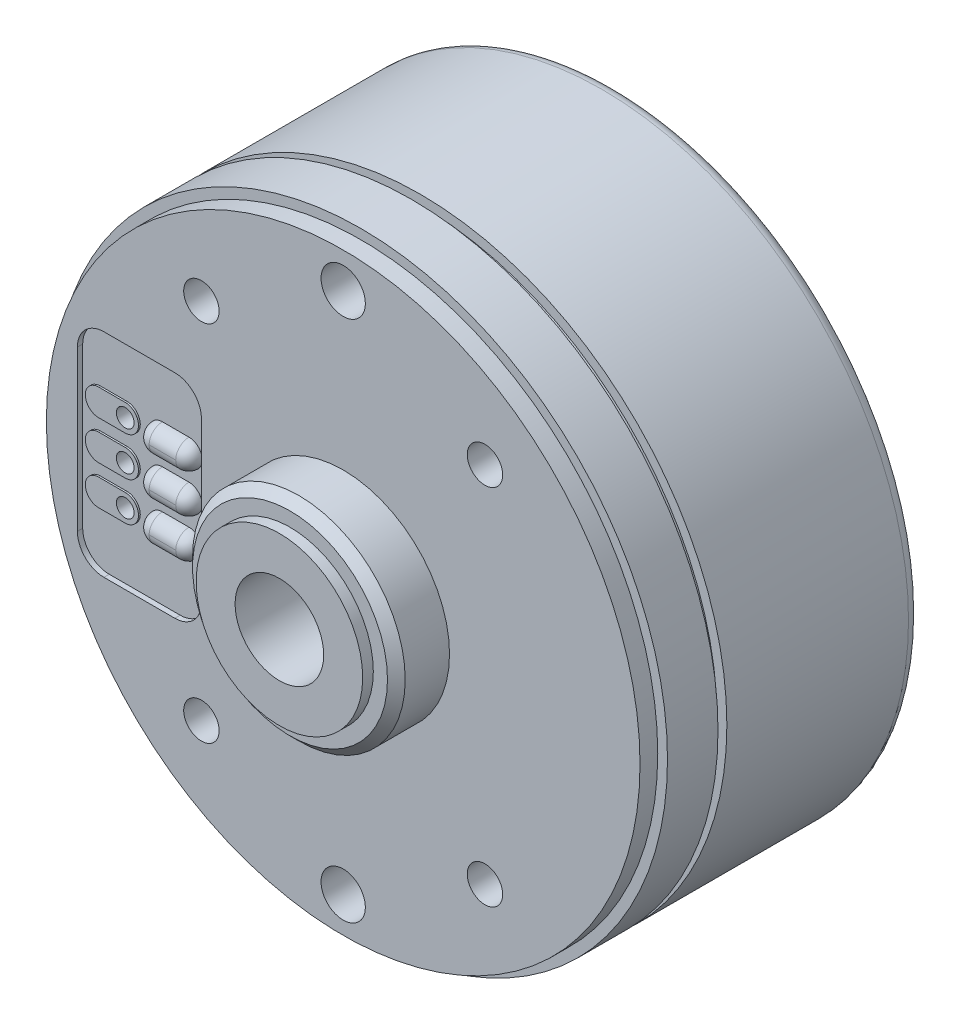
SolidWorks part; units mm, degrees
ref_plane "前视基准面" through (0, 0, 0) normal (0, 0, 1) x (1, 0, 0)
ref_plane "上视基准面" through (0, 0, 0) normal (0, 1, 0) x (1, 0, 0)
ref_plane "右视基准面" through (0, 0, 0) normal (1, 0, 0) x (0, 0, -1)
sketch "草图1" plane through (0, 0, 0) normal (0, 0, 1) x (1, 0, 0)
  line L0 (-101.7763, 0) -> (126.1391, 0) construction
  line L1 (0, -98.9517) -> (0, 107.9553) construction
  line L2 (0, 0) -> (13.767, 17.639) construction
  line L3 (8, 10.25) -> (-8, 10.25) construction
  line L4 (0, 0) -> (-13.767, 17.639) construction
  line L8 (8, 10.25) -> (8, -10.25) construction
  line L9 (8, -10.25) -> (-8, -10.25) construction
  line L10 (-8, 10.25) -> (-8, -10.25) construction
  line L11 (-11.5, -6.8575) -> (-11.5, 7.1069) construction
  line L12 (-9.5, 6) -> (-13.5, 6)
  line L13 (-8, 4.5) -> (-8, -4.5)
  line L14 (-9.5, -6) -> (-13.5, -6)
  line L15 (-15, 4.5) -> (-15, -4.5)
  line L16 (-12.5, 0) -> (-14, 0) construction
  line L17 (-12.5, -0.75) -> (-14, -0.75)
  line L18 (-12.5, 0.75) -> (-14, 0.75)
  line L19 (-12.5, 2.2) -> (-14, 2.2) construction
  line L20 (-12.5, 1.45) -> (-14, 1.45)
  line L21 (-12.5, 2.95) -> (-14, 2.95)
  line L22 (-12.5, -2.2) -> (-14, -2.2) construction
  line L23 (-12.5, -2.95) -> (-14, -2.95)
  line L24 (-12.5, -1.45) -> (-14, -1.45)
  line L25 (-10.5, 0) -> (-9, 0) construction
  line L26 (-10.5, -0.75) -> (-9, -0.75)
  line L27 (-10.5, 0.75) -> (-9, 0.75)
  line L28 (-10.5, -2.2) -> (-9, -2.2) construction
  line L29 (-10.5, -2.95) -> (-9, -2.95)
  line L30 (-10.5, -1.45) -> (-9, -1.45)
  line L31 (-10.5, 2.2) -> (-9, 2.2) construction
  line L32 (-10.5, 1.45) -> (-9, 1.45)
  line L33 (-10.5, 2.95) -> (-9, 2.95)
  circle A0 centre (0, 0) radius 16.75
  circle A1 centre (0, 0) radius 17.3
  circle A2 centre (0, 0) radius 14.75 construction
  circle A3 centre (0, 14.75) radius 1.25
  circle A4 centre (0, -14.75) radius 1.25
  circle A9 centre (-8, 10.25) radius 1
  circle A10 centre (8, 10.25) radius 1
  circle A11 centre (8, -10.25) radius 1
  circle A12 centre (-8, -10.25) radius 1
  circle A13 centre (0, 0) radius 6
  circle A14 centre (0, 0) radius 4.7
  circle A15 centre (0, 0) radius 2.5
  arc A16 (-8, 4.5) -> (-9.5, 6) centre (-9.5, 4.5) ccw
  arc A17 (-9.5, -6) -> (-8, -4.5) centre (-9.5, -4.5) ccw
  arc A18 (-15, -4.5) -> (-13.5, -6) centre (-13.5, -4.5) ccw
  arc A19 (-15, 4.5) -> (-13.5, 6) centre (-13.5, 4.5) cw
  arc A20 (-12.5, -0.75) -> (-12.5, 0.75) centre (-12.5, 0) ccw
  arc A21 (-14, 0.75) -> (-14, -0.75) centre (-14, 0) ccw
  arc A22 (-12.5, 1.45) -> (-12.5, 2.95) centre (-12.5, 2.2) ccw
  arc A23 (-14, 2.95) -> (-14, 1.45) centre (-14, 2.2) ccw
  arc A24 (-12.5, -2.95) -> (-12.5, -1.45) centre (-12.5, -2.2) ccw
  arc A25 (-14, -1.45) -> (-14, -2.95) centre (-14, -2.2) ccw
  arc A26 (-10.5, -0.75) -> (-10.5, 0.75) centre (-10.5, 0) cw
  arc A27 (-9, 0.75) -> (-9, -0.75) centre (-9, 0) cw
  arc A28 (-10.5, -2.95) -> (-10.5, -1.45) centre (-10.5, -2.2) cw
  arc A29 (-9, -1.45) -> (-9, -2.95) centre (-9, -2.2) cw
  arc A30 (-10.5, 1.45) -> (-10.5, 2.95) centre (-10.5, 2.2) cw
  arc A31 (-9, 2.95) -> (-9, 1.45) centre (-9, 2.2) cw
  circle A32 centre (-12.5, 0) radius 0.5
  circle A33 centre (-12.5, 2.2) radius 0.5
  circle A34 centre (-12.5, -2.2) radius 0.5
  point P36 (-8, 6)
  point P39 (-8, -6)
  point P44 (-15, 6)
  point P45 (-11.5, -6)
  point P48 (-13.25, 0)
  point P56 (-13.25, 2.2)
  point P63 (-13.25, -2.2)
  point P69 (-9.75, 0)
  point P76 (-9.75, -2.2)
  point P83 (-9.75, 2.2)
  dimension "D1" = 34.6
  dimension "D2" = 33.5
  dimension "D3" = 29.5
  dimension "D4" = 2.5
  dimension "D6" = 20.5
  dimension "D7" = 2
  dimension "D8" = 9.4
  dimension "D9" = 12
  dimension "D10" = 5
  dimension "D14" = 1.5
  dimension "D16" = 0.75
  dimension "D17" = 1.5
  dimension "D22" = 1
  dimension "D5" = 16
  dimension "D11" = 6
  dimension "D12" = 6
  dimension "D13" = 7
  dimension "D15" = 1.75
  dimension "D19" = 2.2
  dimension "D21" = 2.2
  dimension "D18" = 2
  dimension "D20" = 2
extrude "凸台-拉伸1" add sketch "草图1" along normal blind 3 contours A13
extrude "凸台-拉伸2" add sketch "草图1<3>" along normal blind 3.6 contours A14
sketch "草图1<3>" plane through (0, 0, 0) normal (0, 0, 1) x (1, 0, 0) same geometry as "草图1"
extrude "切除-拉伸1" cut sketch "草图1<4>" along normal blind 3.6 contours A15
sketch "草图1<4>" plane through (0, 0, 0) normal (0, 0, 1) x (1, 0, 0) same geometry as "草图1"
extrude "凸台-拉伸4" add sketch "草图1<7>" against normal blind 15.3 contours A1
sketch "草图1<7>" plane through (0, 0, 0) normal (0, 0, 1) x (1, 0, 0) same geometry as "草图1"
extrude "切除-拉伸3" cut sketch "草图1<8>" against normal blind 4.35 contours A1 A0 region at (-16.8107, 0, 0)
sketch "草图1<8>" plane through (0, 0, 0) normal (0, 0, 1) x (1, 0, 0) same geometry as "草图1"
extrude "凸台-拉伸3" add sketch "草图1<5>" against normal blind 3.85 contours A1
sketch "草图1<5>" plane through (0, 0, 0) normal (0, 0, 1) x (1, 0, 0) same geometry as "草图1"
extrude "切除-拉伸2" cut sketch "草图1<6>" against normal blind 1 contours A1 A0 region at (-16.8107, 0, 0)
sketch "草图1<6>" plane through (0, 0, 0) normal (0, 0, 1) x (1, 0, 0) same geometry as "草图1"
ref_plane "基准面4" through (0, 0, -15.3) normal (0, 0, -1) x (-1, 0, 0)
sketch "草图5" plane through (0, 0, -15.3) normal (0, 0, -1) x (-1, 0, 0)
  line L0 (-30.0955, 0) -> (34.2074, 0) construction
  line L1 (0, 0) -> (-19.6064, 19.6064) construction
  line L2 (0, -23.9486) -> (0, 27.9244) construction
  line L3 (5.25, 5.25) -> (5.25, -5.25) construction
  line L4 (0, 0) -> (19.6064, 19.6064) construction
  line L5 (5.25, 5.25) -> (-5.25, 5.25) construction
  line L6 (-5.25, -5.25) -> (5.25, -5.25) construction
  line L7 (-5.25, -5.25) -> (-5.25, 5.25) construction
  circle A0 centre (0, 0) radius 6.25 construction
  circle A1 centre (6.25, 0) radius 1
  circle A2 centre (0, -6.25) radius 1
  circle A3 centre (-6.25, 0) radius 1
  circle A4 centre (0, 6.25) radius 1
  circle A5 centre (5.25, 5.25) radius 1.25
  circle A6 centre (5.25, -5.25) radius 1.25
  circle A7 centre (-5.25, -5.25) radius 1.25
  circle A8 centre (-5.25, 5.25) radius 1.25
  circle A9 centre (0, 0) radius 3.25
  point P9 (0, 0)
  point P27 (0, 0)
  point P35 (0, 0)
  dimension "D1" = 12.5
  dimension "D3" = 2
  dimension "D5" = 2.5
  dimension "D7" = 6.5
  dimension "D2" = 10.5
  dimension "D4" = 4
  dimension "D6" = 4
extrude "切除-拉伸4" cut sketch "草图5" against normal blind 10.6 contours A9 region at (0, 0, -15.3)
extrude "切除-拉伸5" cut sketch "草图5<3>" against normal blind 2.5 contours A8 | A4 | A5 | A1 | A6 | A2 | A7 | A3 region at (-6.25, 0, -15.3) region at (0, -6.25, -15.3) region at (6.25, 0, -15.3) region at (0, 6.25, -15.3) region at (-5.25, 5.25, -15.3) region at (-5.25, -5.25, -15.3) region at (5.25, -5.25, -15.3) region at (5.25, 5.25, -15.3)
sketch "草图5<3>" plane through (0, 0, -15.3) normal (0, 0, -1) x (-1, 0, 0) same geometry as "草图5"
extrude "切除-拉伸6" cut sketch "草图1<9>" against normal blind 3.8 contours A3 | A10 | A11 | A4 | A12 | A9 region at (0, 14.75, 0) region at (0, -14.75, 0) region at (8, 10.25, 0) region at (8, -10.25, 0) region at (-8, -10.25, 0)
sketch "草图1<9>" plane through (0, 0, 0) normal (0, 0, 1) x (1, 0, 0) same geometry as "草图1"
fillet "圆角1" radius 0.7 1 edges at (17.3, 0, -15.3)
chamfer "倒角1" distance 0.5 angle 45 1 edges at (6, 0, 3)
extrude "切除-拉伸7" cut sketch "草图1<10>" against normal blind 10 contours A15
sketch "草图1<10>" plane through (0, 0, 0) normal (0, 0, 1) x (1, 0, 0) same geometry as "草图1"
extrude "切除-拉伸8" cut sketch "草图1<11>" against normal blind 0.3 contours L12 A19 L15 A18 L14 A17 L13 A16
sketch "草图1<11>" plane through (0, 0, 0) normal (0, 0, 1) x (1, 0, 0) same geometry as "草图1"
extrude "凸台-拉伸5" add sketch "草图1<12>" along normal blind 0.45 separate body contours A27 L27 A26 L26 | A29 L30 A28 L29 | A31 L33 A30 L32 region at (-9.75, 0, 0) region at (-9.75, -2.2, 0) region at (-9.75, 2.2, 0)
sketch "草图1<12>" plane through (0, 0, 0) normal (0, 0, 1) x (1, 0, 0) same geometry as "草图1"
extrude "凸台-拉伸6" add sketch "草图1<14>" against normal blind 0.3 contours L32 A31 L33 A30 | L26 A27 L27 A26 | L29 A29 L30 A28
sketch "草图1<14>" plane through (0, 0, 0) normal (0, 0, 1) x (1, 0, 0) same geometry as "草图1"
fillet "圆角2" radius 0.75 4 edges at (-11.25, 2.2, 0.45) (-9.75, 1.45, 0.45) (-8.25, 2.2, 0.45) (-9.75, 2.95, 0.45)
fillet "圆角3" radius 0.75 4 edges at (-11.25, 0, 0.45) (-9.75, -0.75, 0.45) (-8.25, 0, 0.45) (-9.75, 0.75, 0.45)
fillet "圆角4" radius 0.75 4 edges at (-11.25, -2.2, 0.45) (-9.75, -2.95, 0.45) (-8.25, -2.2, 0.45) (-9.75, -1.45, 0.45)
extrude "凸台-拉伸7" add sketch "草图1<15>" against normal blind 0.3 contours L17 A21 L18 A20 | L20 A23 L21 A22 | L23 A25 L24 A24
sketch "草图1<15>" plane through (0, 0, 0) normal (0, 0, 1) x (1, 0, 0) same geometry as "草图1"
extrude "切除-拉伸9" cut sketch "草图1<13>" against normal blind 2 contours A33 | A32 | A34
sketch "草图1<13>" plane through (0, 0, 0) normal (0, 0, 1) x (1, 0, 0) same geometry as "草图1"
extrude "切除-拉伸10" cut sketch "草图1<16>" against normal blind 0.2 contours L17 A21 L18 A20 | L20 A23 L21 A22 | L23 A25 L24 A24
sketch "草图1<16>" plane through (0, 0, 0) normal (0, 0, 1) x (1, 0, 0) same geometry as "草图1"
